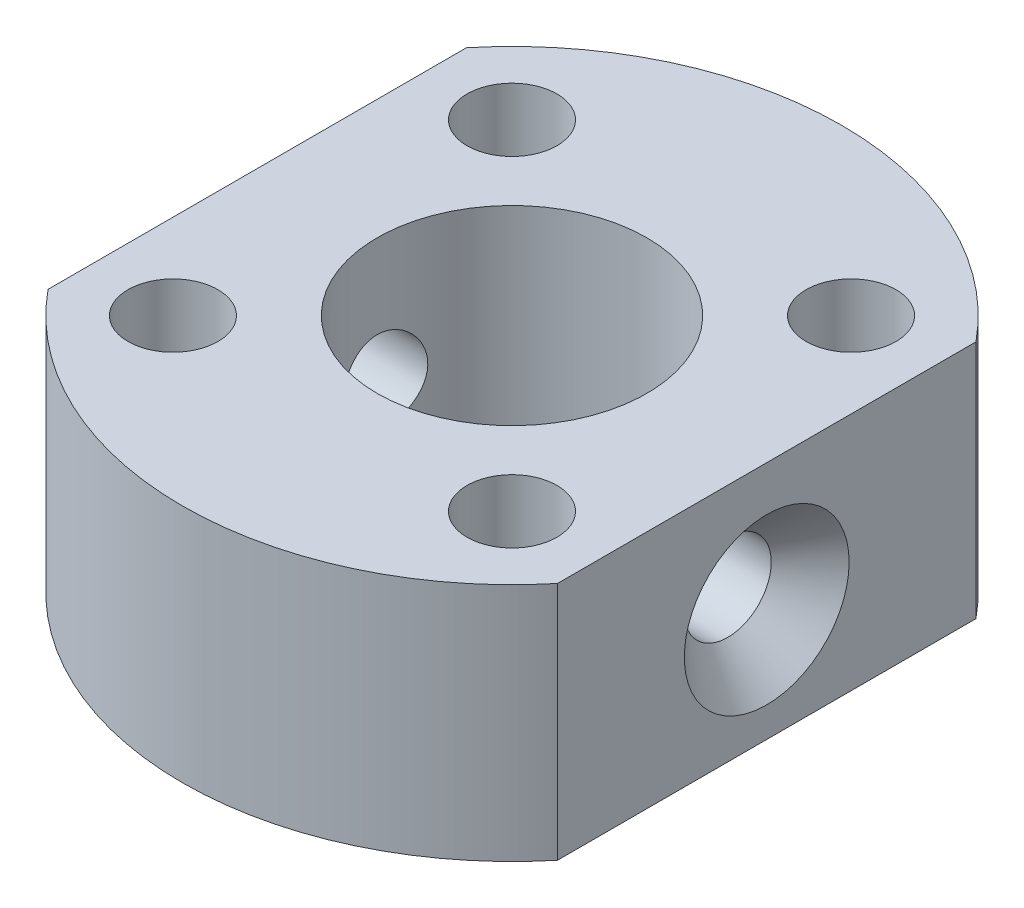
SolidWorks part; units mm, degrees
ref_plane "Front Plane" through (0, 0, 0) normal (0, 0, 1) x (1, 0, 0)
ref_plane "Top Plane" through (0, 0, 0) normal (0, 1, 0) x (1, 0, 0)
ref_plane "Right Plane" through (0, 0, 0) normal (1, 0, 0) x (0, 0, -1)
sketch "Sketch2" plane through (0, 0, 0) normal (0, 1, 0) x (1, 0, 0)
  circle A0 centre (0, 0) radius 11
  dimension "D1" = 22
extrude "Boss-Extrude1" add sketch "Sketch2" along normal blind 8
sketch "Sketch3" plane through (0, 8, 0) normal (0, 1, 0) x (1, 0, 0)
  line L5 (-8.5, 11.5) -> (8.5, 11.5)
  line L6 (-8.5, 11.5) -> (-8.5, -11.5)
  line L7 (-8.5, -11.5) -> (8.5, -11.5)
  line L8 (8.5, 11.5) -> (8.5, -11.5)
  line L9 (0, -11.5) -> (0, 11.5) construction
  line L10 (-8.5, 0) -> (8.5, 0) construction
  point P0 (0, 0)
  dimension "D1" = 8.5
  dimension "D2" = 11.5
extrude "Cut-Extrude1" cut sketch "Sketch3" against normal blind 8 flip side to cut
hole_wizard "Ø9.0 (9) Diameter Hole1" positions "Sketch4" profile "Sketch5" hole size "Ø9.0" standard "ANSI Metric" end condition through all
sketch "Sketch4" plane through (0, 8, 0) normal (0, 1, 0) x (1, 0, 0)
  point P0 (0, 0)
sketch "Sketch5" plane through (0, 8, 0) normal (1, 0, 0) x (0, 0, 1)
  line L0 (0, 0) -> (0, 8)
  line L1 (0, 8) -> (4.5, 8)
  line L2 (4.5, 8) -> (4.5, 0)
  line L5 (4.5, 0) -> (0, 0)
  line L11 (0, -6.35) -> (0, 107.95) construction
  dimension "Thru Hole Dia." = 9
  dimension "Thru Hole Depth" = 8
hole_wizard "CSK for M2.5 Flat Head Machine Screw1" positions "Sketch7" profile "Sketch8" countersink size "M2.5" standard "ANSI Metric" end condition up to next
sketch "Sketch7" plane through (-8.5, 0, 0) normal (-1, 0, 0) x (0, 0, 1)
  line L0 (-6.9821, 8) -> (6.9821, 8) construction
  point P0 (0, 3.75)
  dimension "D1" = 4.25
sketch "Sketch8" plane through (-8.5, 3.75, 0) normal (0, 1, 0) x (0, 0, 1)
  line L0 (0, 0) -> (0, 17)
  line L1 (0, 17) -> (1.45, 17)
  line L2 (1.45, 17) -> (1.45, 1.3)
  line L3 (1.45, 1.3) -> (2.75, 0)
  line L5 (2.75, 0) -> (0, 0)
  line L6 (-1.45, 1.3) -> (-2.75, 0) construction
  line L11 (0, -6.35) -> (0, 107.95) construction
  dimension "Thru Hole Dia." = 2.9
  dimension "Thru Hole Depth" = 17
  dimension "Near C'Sink Dia." = 5.5
  dimension "Near C'Sink Angle" = 90
mirror "Mirror1" about plane through (0, 0, 0) normal (1, 0, 0) of "CSK for M2.5 Flat Head Machine Screw1"
hole_wizard "Ø3.0 (3) Diameter Hole1" positions "Sketch9" profile "Sketch10" hole size "Ø3.0" standard "ANSI Metric"
sketch "Sketch9" plane through (0, 8, 0) normal (0, 1, 0) x (1, 0, 0)
  line L0 (0, 0) -> (-5.6569, 5.6569) construction
  line L2 (-8.5, 6.9821) -> (-8.5, -6.9821) construction
  circle A0 centre (0, 0) radius 8 construction
  point P0 (-5.6569, 5.6569)
  dimension "D1" = 16
  dimension "D2" = 45
sketch "Sketch10" plane through (-5.6569, 8, -5.6569) normal (1, 0, 0) x (0, 0, 1)
  line L0 (0, 0) -> (0, 6.9013)
  line L1 (0, 6.9013) -> (1.5, 6)
  line L2 (1.5, 6) -> (1.5, 0)
  line L5 (1.5, 0) -> (0, 0)
  line L10 (0, 6.9013) -> (-1.5, 6) construction
  line L11 (0, -6.35) -> (0, 107.95) construction
  dimension "Hole Dia." = 3
  dimension "Hole Depth" = 6
  dimension "Drill Angle" = 118
pattern_circular "CirPattern1" count 4 over 360 about axis through (0, 8, 0) along (0, 1, 0) of "Ø3.0 (3) Diameter Hole1"
